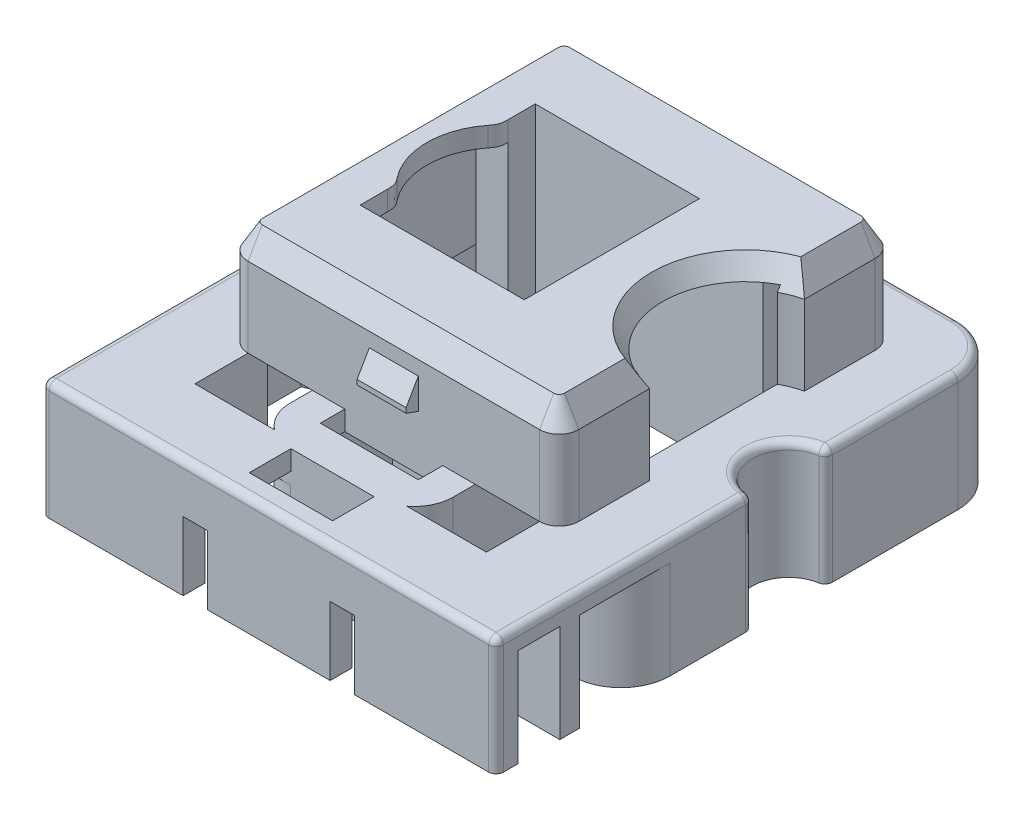
SolidWorks part; units mm, degrees
ref_plane "Front Plane" through (0, 0, 0) normal (0, 0, 1) x (1, 0, 0)
ref_plane "Top Plane" through (0, 0, 0) normal (0, 1, 0) x (1, 0, 0)
ref_plane "Right Plane" through (0, 0, 0) normal (1, 0, 0) x (0, 0, -1)
ref_plane "Floor" through (0, -4, 0) normal (0, -1, 0) x (-1, 0, 0)
sketch "Sketch1" plane through (0, 0, 0) normal (0, 1, 0) x (1, 0, 0)
  line L0 (9.275, -1.5) -> (9.275, -11.95)
  line L1 (-9.275, 8.9) -> (9.275, 8.9)
  line L2 (-9.275, 8.9) -> (-9.275, 1.5)
  line L3 (-9.275, -11.95) -> (9.275, -11.95)
  line L4 (9.275, 8.9) -> (9.275, 1.5)
  line L5 (-9.275, 8.9) -> (9.275, -11.95) construction
  line L6 (-9.275, -11.95) -> (9.275, 8.9) construction
  line L7 (-9.275, -1.5) -> (-9.275, -11.95)
  arc A0 (9.275, 1.5) -> (9.275, -1.5) centre (9.275, 0) ccw
  arc A1 (-9.275, -1.5) -> (-9.275, 1.5) centre (-9.275, 0) ccw
  point P0 (0, -1.525)
  dimension "D4" = 3
  dimension "D5" = 3
  dimension "D1" = 18.55
  dimension "D2" = 20.85
  dimension "D3" = 8.9
extrude "Boss-Extrude1" add sketch "Sketch1" along normal blind 0.8
sketch "Sketch2" plane through (0, 0.8, 0) normal (0, 1, 0) x (1, 0, 0)
  line L0 (6.75, -3.1623) -> (6.75, -6.85)
  line L1 (-6.75, 6.85) -> (6.75, 6.85)
  line L2 (-6.75, 6.85) -> (-6.75, -6.85)
  line L3 (-6.75, -6.85) -> (6.75, -6.85)
  line L4 (6.75, 6.85) -> (6.75, 3.1623)
  line L5 (-6.75, 6.85) -> (6.75, -6.85) construction
  line L6 (-6.75, -6.85) -> (6.75, 6.85) construction
  arc A0 (6.75, 3.1623) -> (6.75, -3.1623) centre (7.5, 0) ccw
  point P0 (0, 0)
  point P7 (13.3281, 0.717)
  point P12 (7.5, 0)
  dimension "D3" = 6.5
  dimension "D1" = 13.5
  dimension "D2" = 13.7
  dimension "D4" = 7.5
extrude "Boss-Extrude2" add sketch "Sketch2" along normal blind 4.25
sketch "Sketch15" plane through (0, 0, 0) normal (0, -1, 0) x (1, 0, 0)
  line L1 (5.95, 6.05) -> (-5.95, 6.05)
  line L2 (5.95, 6.05) -> (5.95, -6.05)
  line L3 (5.95, -6.05) -> (-5.95, -6.05)
  line L4 (-5.95, 6.05) -> (-5.95, -6.05)
  line L5 (5.95, 6.05) -> (-5.95, -6.05) construction
  line L6 (5.95, -6.05) -> (-5.95, 6.05) construction
  point P0 (0, 0)
  point P6 (0, 0)
  point P7 (0, 0)
  point P9 (0, 0)
  dimension "D1" = 11.9
  dimension "D2" = 12.1
extrude "Cut-Extrude3" cut sketch "Sketch15" against normal blind 4.25
ref_plane "Plane2" through (0, 2.3, 0) normal (0, 1, 0) x (1, 0, 0)
sketch "Sketch23" plane through (0, 5.05, 0) normal (0, 1, 0) x (1, 0, 0)
  line L0 (0, -1000) -> (0, 49000) construction
  line L1 (1.9, -1001.0023) -> (1.9, 48998.9977) construction
  line L2 (-2.5, -1002.0635) -> (-2.5, 48997.9365) construction
  line L3 (-4.5, -1002.4785) -> (-4.5, 48997.5215) construction
  line L4 (-1000, 0) -> (49000, 0) construction
  line L6 (-4.65, 3.575) -> (2.05, 3.575)
  line L7 (-4.65, 3.575) -> (-4.65, -3.575)
  line L8 (-4.65, -3.575) -> (2.05, -3.575)
  line L9 (2.05, 3.575) -> (2.05, -3.575)
  line L10 (-4.65, 3.575) -> (2.05, -3.575) construction
  line L11 (-4.65, -3.575) -> (2.05, 3.575) construction
  point P10 (-1.3, 0)
  dimension "D1" = 1.9
  dimension "D2" = 2.5
  dimension "D3" = 2
  dimension "D4" = 7.15
  dimension "D5" = 0.15
  dimension "D6" = 0.15
extrude "Cut-Extrude6" cut sketch "Sketch23" against normal up to surface (0.8 mm away) up to face at (1.7, 4.25, 0)
sketch "Sketch5" plane through (0, 5.05, 0) normal (0, 1, 0) x (1, 0, 0)
  circle A0 centre (-2.5, 0) radius 2.75 construction
  circle A1 centre (7.5, 0) radius 2.75 construction
  circle A2 centre (-2.5, 0) radius 3
  point P0 (-2.5, 0)
  dimension "D2" = 5.5
  dimension "D4" = 0.25
  dimension "D1" = 2.5
  dimension "D3" = 10
extrude "Cut-Extrude7" cut sketch "Sketch5" against normal up to surface (0.8 mm away) up to face at (-1.3, 4.25, 0)
sketch "Sketch6" plane through (0, 0, 6.85) normal (0, 0, 1) x (1, 0, 0)
  line L0 (-6.75, 0.8) -> (6.75, 0.8) construction
  line L1 (-1, 2.6) -> (1, 2.6)
  line L2 (-1, 2.6) -> (-1, 2.4)
  line L3 (-1, 2.4) -> (1, 2.4)
  line L4 (1, 2.6) -> (1, 2.4)
  line L5 (-1, 2.6) -> (1, 2.4) construction
  line L6 (-1, 2.4) -> (1, 2.6) construction
  point P0 (0, 2.5)
  dimension "D1" = 1.6
  dimension "D2" = 0.2
  dimension "D3" = 2
extrude "Boss-Extrude4" add sketch "Sketch6" along normal blind 0.5
draft "Draft1" type of draft neutral plane draft angle 60 faces to draft 1 face at (0, 2.6, 7.1) neutral plane through (0, 0, 7.35) neutral plane normal (0, 0, 1) parameters "D1"=60
draft "Draft4" type of draft neutral plane draft angle 20 faces to draft 1 face at (0, 2.4, 7.1) neutral plane through (0, 0, 7.35) neutral plane normal (0, 0, 1) parameters "D1"=20
sketch "Sketch7" plane through (0, 0.8, 0) normal (0, 1, 0) x (1, 0, 0)
  line L0 (-6.75, -6.85) -> (6.75, -6.85) construction
  line L1 (-2, -6.85) -> (2, -6.85)
  line L2 (-2, -6.85) -> (-2, -7.85)
  line L3 (-2, -7.85) -> (2, -7.85)
  line L4 (2, -6.85) -> (2, -7.85)
  line L5 (-2, -6.85) -> (2, -7.85) construction
  line L6 (-2, -7.85) -> (2, -6.85) construction
  point P0 (0, -7.35)
  dimension "D1" = 1
  dimension "D2" = 4
extrude "Cut-Extrude1" cut sketch "Sketch7" against normal through all
mirror "Mirror1" about plane through (0, 0, 0) normal (0, 0, 1) of "Draft4", "Draft1", "Boss-Extrude4", "Cut-Extrude1"
sketch "Sketch8" plane through (0, 0, 0) normal (0, 1, 0) x (1, 0, 0)
  line L1 (9.275, -11.05) -> (-9.275, -11.05)
  line L2 (9.275, -11.05) -> (9.275, -11.95)
  line L3 (9.275, -11.95) -> (-9.275, -11.95)
  line L4 (-9.275, -11.05) -> (-9.275, -11.95)
  line L5 (9.275, -11.05) -> (-9.275, -11.95) construction
  line L6 (9.275, -11.95) -> (-9.275, -11.05) construction
  line L8 (-9.275, -11.95) -> (9.275, -11.95) construction
  point P0 (0, -11.5)
  dimension "D1" = 0.9
extrude "Boss-Extrude5" add sketch "Sketch8" against normal up to surface (4 mm away) up to plane "Floor"
sketch "Sketch9" plane through (0, -4, 0) normal (0, -1, 0) x (-1, 0, 0)
  line L0 (9.275, -11.95) -> (-9.275, -11.95) construction
  line L1 (-9.275, -11.05) -> (9.275, -11.05) construction
  line L7 (-2.5, -11.95) -> (-3.5, -11.95)
  line L8 (-2.5, -11.95) -> (-2.5, -11.05)
  line L9 (-2.5, -11.05) -> (-3.5, -11.05)
  line L10 (-3.5, -11.95) -> (-3.5, -11.05)
  line L11 (-2.5, -11.95) -> (-3.5, -11.05) construction
  line L12 (-2.5, -11.05) -> (-3.5, -11.95) construction
  point P5 (-3, -11.5)
  dimension "D1" = 1
  dimension "D2" = 2.5
extrude "Cut-Extrude2" cut sketch "Sketch9" against normal blind 2.8
mirror "Mirror2" about plane through (0, 0, 0) normal (1, 0, 0) of "Cut-Extrude2"
sketch "Sketch11" plane through (0, 0, 0) normal (0, -1, 0) x (1, 0, 0)
  line L0 (9.275, 11.05) -> (9.275, 1.5) construction
  line L1 (5.95, 9.35) -> (9.275, 9.35)
  line L2 (5.95, 9.35) -> (5.95, 6.05)
  line L3 (9.275, 8.55) -> (6.75, 8.55)
  line L4 (9.275, 9.35) -> (9.275, 8.55)
  line L5 (9.275, 11.05) -> (-9.275, 11.05) construction
  line L6 (6.75, 8.55) -> (6.75, 6.85)
  line L7 (6.75, 6.85) -> (7.275, 6.85)
  line L8 (9.275, 4.85) -> (9.275, 1.5)
  line L9 (5.95, 6.05) -> (7.275, 6.05)
  line L10 (8.475, 4.85) -> (8.475, 2.1564)
  line L11 (9.275, -1.5) -> (9.275, -8.9)
  line L12 (9.275, -1.5) -> (9.275, -8.9) construction
  line L13 (8.475, -8.9) -> (8.475, -2.1564)
  line L14 (9.275, -8.9) -> (-9.275, -8.9) construction
  line L15 (8.475, -8.9) -> (9.275, -8.9)
  line L16 (5.95, -6.05) -> (5.95, 6.05) construction
  line L17 (5.95, 6.05) -> (-5.95, 6.05) construction
  arc A0 (9.275, 1.5) -> (9.275, -1.5) centre (9.275, 0) ccw
  arc A1 (8.475, 2.1564) -> (8.475, -2.1564) centre (9.275, 0) ccw
  arc A2 (7.275, 6.05) -> (8.475, 4.85) centre (7.275, 4.85) cw
  arc A3 (7.275, 6.85) -> (9.275, 4.85) centre (7.275, 4.85) cw
  point P24 (9.275, 6.85)
  dimension "D4" = 3
  dimension "D5" = 4.6
  dimension "D10" = 1.2
  dimension "D11" = 2
  dimension "D1" = 1.7
  dimension "D2" = 0.8
  dimension "D6" = 0.8
  dimension "D7" = 0.8
  dimension "D8" = 0.8
  dimension "D12" = 0.8
extrude "Boss-Extrude6" add sketch "Sketch11" along normal up to surface (4 mm away) up to plane "Floor"
sketch "Sketch12" plane through (0, 0, 0) normal (0, -1, 0) x (1, 0, 0)
  line L1 (5.95, 11.05) -> (6.75, 11.05)
  line L2 (5.95, 11.05) -> (5.95, 9.35)
  line L3 (5.95, 9.35) -> (6.75, 9.35)
  line L4 (6.75, 11.05) -> (6.75, 9.35)
  line L5 (9.275, 11.05) -> (-9.275, 11.05) construction
  line L6 (9.275, 9.35) -> (5.95, 9.35) construction
  line L7 (5.95, 9.35) -> (5.95, 6.05) construction
  line L8 (6.75, 6.85) -> (6.75, 8.55) construction
extrude "Boss-Extrude7" add sketch "Sketch12" along normal blind 1.5
mirror "Mirror3" about plane through (0, 0, 0) normal (1, 0, 0) of "Boss-Extrude7", "Boss-Extrude6"
sketch "Sketch19" plane through (0, 0, 0) normal (0, -1, 0) x (1, 0, 0)
  line L0 (8.475, -8.9) -> (-8.475, -8.9) construction
  line L1 (-4.65, -3.575) -> (4.65, -3.575)
  line L2 (-4.65, -3.575) -> (-4.65, -8.9)
  line L3 (-4.65, -8.9) -> (4.65, -8.9)
  line L4 (4.65, -3.575) -> (4.65, -8.9)
  line L5 (-4.65, -3.575) -> (4.65, -8.9) construction
  line L6 (-4.65, -8.9) -> (4.65, -3.575) construction
  line L7 (-4.65, -3.575) -> (2.05, -3.575) construction
  line L8 (-3.85, -8.1) -> (3.85, -8.1)
  line L9 (-3.85, -8.1) -> (-3.85, -4.375)
  line L10 (-3.85, -4.375) -> (3.85, -4.375)
  line L11 (3.85, -8.1) -> (3.85, -4.375)
  line L12 (-3.85, -8.1) -> (3.85, -4.375) construction
  line L13 (-3.85, -4.375) -> (3.85, -8.1) construction
  line L14 (-4.65, -2.0922) -> (-4.65, -3.575) construction
  point P0 (0, -6.2375)
  point P7 (0, -8.9)
  point P9 (0, -6.2375)
  dimension "D3" = 0.8
  dimension "D4" = 0.8
sketch "Sketch13" plane through (0, 0, 0) normal (0, -1, 0) x (1, 0, 0)
  line L0 (8.475, -8.9) -> (-8.475, -8.9) construction
  line L1 (8.475, -8.1) -> (-8.475, -8.1)
  line L2 (8.475, -8.1) -> (8.475, -8.9)
  line L3 (8.475, -8.9) -> (-8.475, -8.9)
  line L4 (-8.475, -8.1) -> (-8.475, -8.9)
  line L5 (8.475, -8.1) -> (-8.475, -8.9) construction
  line L6 (8.475, -8.9) -> (-8.475, -8.1) construction
  point P0 (0, -8.5)
  point P7 (0, -8.9)
  dimension "D1" = 0.8
extrude "Boss-Extrude8" add sketch "Sketch13" along normal up to surface (4 mm away) up to plane "Floor"
fillet "Fillet6" radius 1 2 edges at (-4.65, 4.65, 2.0922) (-4.65, 4.65, -2.0922) conic rho 0.65
fillet "Fillet1" radius 1.2 2 edges at (8.475, -2, -8.1) (-8.475, -2, -8.1)
fillet "Fillet2" radius 2 2 edges at (9.275, -1.6, -8.9) (-9.275, -1.6, -8.9)
fillet "Fillet3" radius 0.3 16 edges at (9.275, 0.8, -4.2) (8.6892, 0.8, -8.3142) (0, 0.8, -8.9) (-8.6892, 0.8, -8.3142) (7.775, 0.8, 0) (-7.775, 0.8, 0) (-9.275, 0.8, 6.725) (0, 0.8, 11.95) (9.275, 0.8, 6.725) (-9.275, 0.8, -4.2) (-9.275, -1.6, -1.5) (-9.275, -1.6, 1.5) (9.275, -1.6, -1.5) (9.275, -1.6, 1.5) (-9.275, -1.6, 11.95) (9.275, -1.6, 11.95)
fillet "Fillet5" radius 0.8 4 edges at (-6.75, 2.925, -6.85) (6.75, 2.925, -6.85) (-6.75, 2.925, 6.85) (6.75, 2.925, 6.85)
chamfer "Chamfer1" distance 1 angle 30 10 edges at (6.5157, 5.05, -6.6157) (0, 5.05, -6.85) (-6.5157, 5.05, -6.6157) (-6.75, 5.05, 0) (-6.5157, 5.05, 6.6157) (6.75, 5.05, -4.6061) (0, 5.05, 6.85) (6.75, 5.05, 4.6061) (6.5157, 5.05, 6.6157) (4.25, 5.05, 0) first distance on face at (6.4328, 2.925, -6.5328) first distance on face at (0, 2.842, -6.85) first distance on face at (-6.4328, 2.925, -6.5328) first distance on face at (-6.75, 2.925, 0) first distance on face at (-6.4328, 2.925, 6.5328) first distance on face at (6.75, 2.925, -4.6061) first distance on face at (0, 1.6625, 6.85) first distance on face at (6.75, 2.925, 4.6061) first distance on face at (6.4328, 2.925, 6.5328) first distance on face at (5.8225, 2.725, 0)
sketch "Sketch14" plane through (0, 0, 0) normal (0, -1, 0) x (1, 0, 0)
  line L0 (9.275, 9.35) -> (6.75, 9.35) construction
  line L1 (-1.725, 9.35) -> (1.725, 9.35)
  line L2 (-3.325, 7.75) -> (-3.325, 3.575)
  line L3 (-3.325, 3.575) -> (3.325, 3.575)
  line L4 (3.325, 7.75) -> (3.325, 3.575)
  line L5 (-3.325, 9.35) -> (3.325, 3.575) construction
  line L6 (-3.325, 3.575) -> (3.325, 9.35) construction
  line L7 (2.05, 3.575) -> (-4.65, 3.575) construction
  line L8 (-1.725, 8.55) -> (1.725, 8.55)
  line L9 (-2.525, 7.75) -> (-2.525, 4.375)
  line L10 (-2.525, 4.375) -> (2.525, 4.375)
  line L11 (2.525, 7.75) -> (2.525, 4.375)
  line L12 (-2.525, 8.55) -> (2.525, 4.375) construction
  line L13 (-2.525, 4.375) -> (2.525, 8.55) construction
  arc A0 (-1.725, 9.35) -> (-3.325, 7.75) centre (-1.725, 7.75) ccw
  arc A1 (1.725, 9.35) -> (3.325, 7.75) centre (1.725, 7.75) cw
  arc A2 (-1.725, 8.55) -> (-2.525, 7.75) centre (-1.725, 7.75) ccw
  arc A3 (1.725, 8.55) -> (2.525, 7.75) centre (1.725, 7.75) cw
  point P0 (0, 6.4625)
  point P10 (0, 6.4625)
  dimension "D5" = 1.6
  dimension "D6" = 0.8
  dimension "D1" = 6.65
  dimension "D3" = 0.8
  dimension "D4" = 0.8
extrude "Boss-Extrude9" add sketch "Sketch14" along normal up to surface (4 mm away) up to plane "Floor"
sketch "Sketch16" plane through (0, 0, 0) normal (0, -1, 0) x (1, 0, 0)
  line L8 (-3.325, 6.05) -> (-3.325, 3.575)
  line L9 (-2.525, 6.05) -> (-3.325, 6.05)
  line L10 (-2.525, 4.375) -> (-2.525, 6.05)
  line L11 (2.525, 4.375) -> (-2.525, 4.375)
  line L12 (2.525, 6.05) -> (2.525, 4.375)
  line L13 (3.325, 6.05) -> (2.525, 6.05)
  line L14 (3.325, 3.575) -> (3.325, 6.05)
  line L15 (-3.325, 3.575) -> (3.325, 3.575)
  line L16 (-3.325, 6.05) -> (-3.325, 3.575)
  line L17 (-2.525, 6.05) -> (-3.325, 6.05)
  line L18 (-2.525, 4.375) -> (-2.525, 6.05)
  line L19 (2.525, 4.375) -> (-2.525, 4.375)
  line L20 (2.525, 6.05) -> (2.525, 4.375)
  line L21 (3.325, 6.05) -> (2.525, 6.05)
  line L22 (3.325, 3.575) -> (3.325, 6.05)
  line L23 (-3.325, 3.575) -> (3.325, 3.575)
  dimension "D1" = 0
extrude "Boss-Extrude10" add sketch "Sketch16" against normal up to surface (4.25 mm away) up to face at (-3.0281, 4.25, 0.2928)
sketch "Sketch17" plane through (0, 0, 0) normal (0, -1, 0) x (1, 0, 0)
  line L0 (5.95, 11.05) -> (-5.95, 11.05) construction
  line L1 (-1.7, 11.05) -> (1.7, 11.05)
  line L2 (-1.7, 11.05) -> (-1.7, 9.35)
  line L3 (-1.7, 9.35) -> (1.7, 9.35)
  line L4 (1.7, 11.05) -> (1.7, 9.35)
  line L5 (-1.7, 11.05) -> (1.7, 9.35) construction
  line L6 (-1.7, 9.35) -> (1.7, 11.05) construction
  line L7 (1.725, 9.35) -> (-1.725, 9.35) construction
  point P0 (0, 10.2)
  dimension "D1" = 3.4
extrude "Cut-Extrude4" cut sketch "Sketch17" against normal through all
sketch "Sketch18" plane through (0, 0, 11.05) normal (0, 0, -1) x (-1, 0, 0)
  line L1 (1.4, -3.1) -> (-1.4, -3.1)
  line L2 (1.4, -3.1) -> (1.4, -3.3)
  line L3 (1.4, -3.3) -> (-1.4, -3.3)
  line L4 (-1.4, -3.1) -> (-1.4, -3.3)
  line L5 (1.4, -3.1) -> (-1.4, -3.3) construction
  line L6 (1.4, -3.3) -> (-1.4, -3.1) construction
  line L7 (-6.75, -1.5) -> (-5.95, -1.5) construction
  point P0 (0, -3.2)
  dimension "D1" = 1.6
  dimension "D2" = 0.2
  dimension "D3" = 2.8
extrude "Boss-Extrude11" add sketch "Sketch18" along normal blind 0.25
draft "Draft2" type of draft neutral plane draft angle 60 faces to draft 1 face at (0, -3.3, 10.925) neutral plane through (0, 0, 10.8) neutral plane normal (0, 0, -1) parameters "D1"=60
draft "Draft3" type of draft neutral plane draft angle 20 faces to draft 1 face at (0, -3.1, 10.925) neutral plane through (0, 0, 10.8) neutral plane normal (0, 0, -1) parameters "D1"=20
ref_plane "Plane4" through (0, 0, 10.2) normal (0, 0, -1) x (-1, 0, 0)
mirror "Mirror4" about plane through (0, 0, 10.2) normal (0, 0, -1) of "Draft3", "Draft2", "Boss-Extrude11"
extrude "Boss-Extrude12" add sketch "Sketch19" along normal up to surface (4 mm away) up to plane "Floor"
sketch "Sketch20" plane through (0, 0, 0) normal (0, -1, 0) x (1, 0, 0)
  line L8 (4.65, -6.05) -> (4.65, -3.575)
  line L9 (3.85, -6.05) -> (4.65, -6.05)
  line L10 (3.85, -4.375) -> (3.85, -6.05)
  line L11 (-3.85, -4.375) -> (3.85, -4.375)
  line L12 (-3.85, -6.05) -> (-3.85, -4.375)
  line L13 (-4.65, -6.05) -> (-3.85, -6.05)
  line L14 (-4.65, -3.575) -> (-4.65, -6.05)
  line L15 (4.65, -3.575) -> (-4.65, -3.575)
  line L16 (4.65, -6.05) -> (4.65, -3.575)
  line L17 (3.85, -6.05) -> (4.65, -6.05)
  line L18 (3.85, -4.375) -> (3.85, -6.05)
  line L19 (-3.85, -4.375) -> (3.85, -4.375)
  line L20 (-3.85, -6.05) -> (-3.85, -4.375)
  line L21 (-4.65, -6.05) -> (-3.85, -6.05)
  line L22 (-4.65, -3.575) -> (-4.65, -6.05)
  line L23 (4.65, -3.575) -> (-4.65, -3.575)
  dimension "D1" = 0
extrude "Boss-Extrude13" add sketch "Sketch20" against normal up to surface (4.25 mm away) up to face at (-0.7856, 4.25, 1.1996)
sketch "Sketch21" plane through (0, 0, 0) normal (0, -1, 0) x (1, 0, 0)
  line L0 (2.7, 11.05) -> (2.7, 9.0186) construction
  line L1 (5.95, 11.05) -> (1.7, 11.05) construction
  line L2 (1.7, 9.35) -> (1.7, 11.05) construction
  line L3 (2.7, 9.0186) -> (5.95, 9.0186)
  line L9 (5.95, 11.05) -> (1.7, 11.05)
  line L10 (1.7, 11.05) -> (1.7, 9.35)
  line L11 (1.7, 9.35) -> (1.725, 9.35)
  line L12 (3.325, 7.75) -> (3.325, 6.05)
  line L13 (3.325, 6.05) -> (5.95, 6.05)
  line L14 (5.95, 6.05) -> (5.95, 11.05)
  line L18 (3.325, 7.75) -> (3.325, 6.05)
  line L19 (3.325, 6.05) -> (5.95, 6.05)
  line L20 (5.95, 6.05) -> (5.95, 9.0186)
  arc A0 (3.325, 7.75) -> (1.725, 9.35) centre (1.725, 7.75) ccw construction
  arc A2 (3.325, 7.75) -> (1.725, 9.35) centre (1.725, 7.75) ccw
  arc A3 (3.325, 7.75) -> (2.7, 9.0186) centre (1.725, 7.75) ccw
  dimension "D1" = 1
  dimension "D2" = 0
extrude "Cut-Extrude5" cut sketch "Sketch21" against normal up to surface (0.8 mm away) up to face at (0, 0.8, 10.2)
sketch "Sketch22" plane through (0, 0, 0) normal (0, -1, 0) x (1, 0, 0)
  line L0 (1.725, 9.35) -> (5.95, 9.35)
  line L5 (2.7, 9.0186) -> (5.95, 9.0186)
  line L6 (5.95, 9.0186) -> (5.95, 11.05)
  line L7 (5.95, 11.05) -> (1.7, 11.05)
  line L8 (1.7, 11.05) -> (1.7, 9.35)
  line L9 (1.7, 9.35) -> (1.725, 9.35)
  line L10 (2.7, 9.0186) -> (5.95, 9.0186)
  line L11 (5.95, 9.0186) -> (5.95, 9.35)
  arc A1 (2.7, 9.0186) -> (1.725, 9.35) centre (1.725, 7.75) ccw
  arc A2 (2.7, 9.0186) -> (1.725, 9.35) centre (1.725, 7.75) ccw
  dimension "D1" = 0
extrude "Boss-Extrude14" add sketch "Sketch22" along normal blind 0.5
mirror "Mirror5" about plane through (0, 0, 0) normal (1, 0, 0) of "Boss-Extrude14", "Cut-Extrude5"
chamfer "Chamfer2" distance 0.5 angle 30 2 edges at (4.6375, 0.8, 6.05) (-4.6375, 0.8, 6.05) first distance on face at (4.6375, 2.525, 6.05) first distance on face at (-4.6375, 0.8, 6.45)
sketch "Sketch24" plane through (0, 4.25, 0) normal (0, -1, 0) x (1, 0, 0)
  line L0 (2.05, 3.575) -> (2.05, -3.575) construction
  line L1 (2.05, 1.075) -> (3.325, 1.075)
  line L2 (2.05, 1.075) -> (2.05, 3.575)
  line L3 (2.05, 3.575) -> (3.325, 3.575)
  line L4 (3.325, 1.075) -> (3.325, 3.575)
  dimension "D1" = 2.5
extrude "Boss-Extrude15" add sketch "Sketch24" along normal up to surface (8.25 mm away) up to plane "Floor"
sketch "Sketch25" plane through (0, 4.25, 0) normal (0, -1, 0) x (1, 0, 0)
  line L0 (-4.65, -2.4653) -> (-5.95, -2.4653)
  line L9 (-4.65, 2.4653) -> (-4.65, 3.575)
  line L10 (-4.65, 3.575) -> (-3.325, 3.575)
  line L11 (-3.325, 3.575) -> (-3.325, 6.05)
  line L12 (-3.325, 6.05) -> (-5.95, 6.05)
  line L13 (-5.95, 6.05) -> (-5.95, -6.05)
  line L14 (-5.95, -6.05) -> (-4.65, -6.05)
  line L15 (-4.65, -6.05) -> (-4.65, -3.575)
  line L17 (-4.65, -3.575) -> (-4.65, -2.4653)
  line L22 (-5.95, -2.4653) -> (-5.95, -6.05)
  line L23 (-5.95, -6.05) -> (-4.65, -6.05)
  line L24 (-4.65, -6.05) -> (-4.65, -3.575)
  line L26 (-4.65, -3.575) -> (-4.65, -2.4653)
  arc A1 (-4.8625, 1.8489) -> (-4.8625, -1.8489) centre (-2.5, 0) ccw
  spline S2 degree 2 poles (-748.2714, -666.988) (-11.4668, -8.1889) (-4.7633, 1.9848) (-4.7116, 2.0633) (-4.6871, 2.1335) (-4.6638, 2.2003) (-4.6556, 2.2972) (-3.7384, 13.1006) (-152.9575, 991.4046) knots -43.936804 -43.936804 -43.936804 0.25 0.25 0.5 0.5 0.75 0.75 41.674386 41.674386 41.674386 only from (-4.8625, 1.8489) to (-4.65, 2.4653)
  spline S3 degree 2 poles (-177.8705, -987.3482) (-3.6644, -14.4404) (-4.6556, -2.2971) (-4.6633, -2.2035) (-4.6873, -2.1331) (-4.7101, -2.0661) (-4.7633, -1.9848) (-10.6994, 7.0882) (-731.1525, 685.5367) knots -43.936804 -43.936804 -43.936804 0.25 0.25 0.5 0.5 0.75 0.75 41.674386 41.674386 41.674386 only from (-4.65, -2.4653) to (-4.8625, -1.8489)
  dimension "D1" = 0
extrude "Boss-Extrude16" add sketch "Sketch25" along normal up to surface (8.25 mm away) up to plane "Floor"
